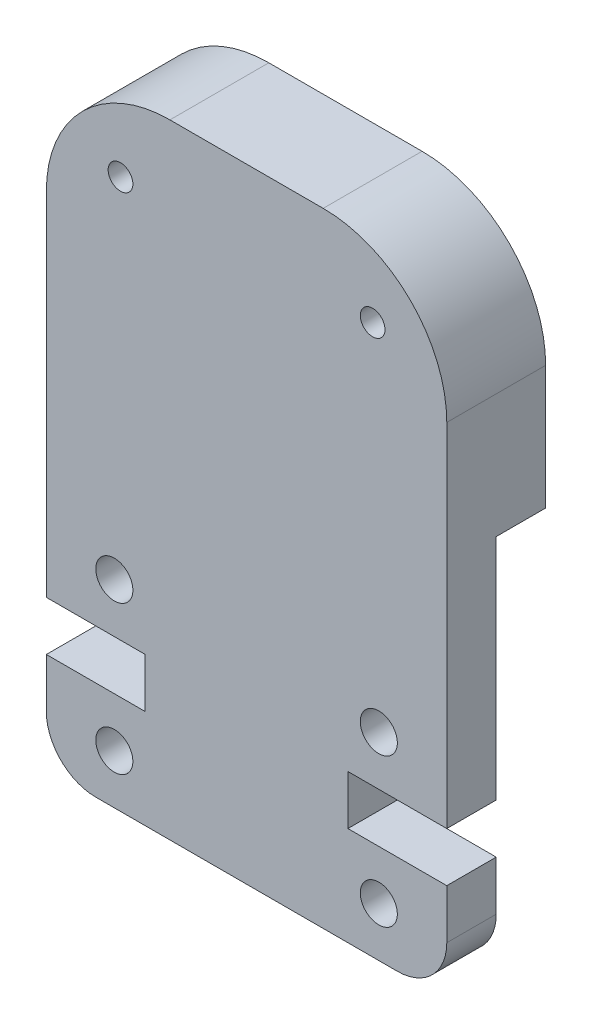
SolidWorks part; units mm, degrees
ref_plane "Front Plane" through (0, 0, 0) normal (0, 0, 1) x (1, 0, 0)
ref_plane "Top Plane" through (0, 0, 0) normal (0, 1, 0) x (1, 0, 0)
ref_plane "Right Plane" through (0, 0, 0) normal (1, 0, 0) x (0, 0, -1)
sketch "Sketch1" plane through (0, 0, 0) normal (0, 0, 1) x (1, 0, 0)
  line L0 (8.1, 25.23) -> (8.1, 0) construction
  line L1 (2, 0) -> (14.2, 0)
  line L2 (5, 25.23) -> (11.2, 25.23)
  line L3 (12.2, 4) -> (16.2, 4)
  line L4 (12.2, 6) -> (12.2, 4)
  line L5 (16.2, 6) -> (12.2, 6)
  line L6 (16.2, 2) -> (16.2, 4)
  line L7 (16.2, 20.23) -> (16.2, 6)
  line L22 (0, 20.23) -> (0, 6)
  line L33 (0, 2) -> (0, 4)
  line L34 (0, 6) -> (4, 6)
  line L36 (4, 6) -> (4, 4)
  line L37 (4, 4) -> (0, 4)
  circle A0 centre (13.45, 2) radius 0.75
  arc A1 (16.2, 2) -> (14.2, 0) centre (14.2, 2) cw
  circle A2 centre (13.2, 22.23) radius 0.5
  arc A3 (11.2, 25.23) -> (16.2, 20.23) centre (11.2, 20.23) cw
  circle A4 centre (2.75, 8) radius 0.75
  circle A5 centre (13.45, 8) radius 0.75
  arc A17 (5, 25.23) -> (0, 20.23) centre (5, 20.23) ccw
  circle A19 centre (3, 22.23) radius 0.5
  arc A21 (0, 2) -> (2, 0) centre (2, 2) ccw
  circle A23 centre (2.75, 2) radius 0.75
  dimension "D1" = 1
  dimension "D2" = 6
  dimension "D3" = 5
  dimension "D4" = 2
  dimension "D5" = 3
  dimension "D6" = 2.75
  dimension "D7" = 8.1
  dimension "D8" = 2.75
  dimension "D9" = 4
  dimension "D12" = 3
  dimension "D13" = 25.23
extrude "Boss-Extrude1" add sketch "Sketch1" along normal blind 4
sketch "Sketch2" plane through (0, 0, 0) normal (0, 0, 1) x (1, 0, 0)
  line L0 (0, 0) -> (16.2, 0)
  line L1 (16.2, 0) -> (16.2, 15.23)
  line L2 (16.2, 15.23) -> (0, 15.23)
  line L3 (0, 15.23) -> (0, 0)
  dimension "D1" = 15.23
extrude "Cut-Extrude1" cut sketch "Sketch2" along normal blind 2
equation "\"D7@Sketch1\"= \"fingerWidth@parametersSketch@prostheticParameters.SLDPRT\" / 2 'DIP width"
equation "\"D13@Sketch1\"= \"HL@parametersSketch@prostheticParameters.SLDPRT\" * 0.158 - 4 'DIP length - Sil. Sht DIP"
equation "\"D1@Sketch2\"= \"HL@parametersSketch@prostheticParameters.SLDPRT\" * 0.158 - 4 - 10 'DIP Cut fingertip"
